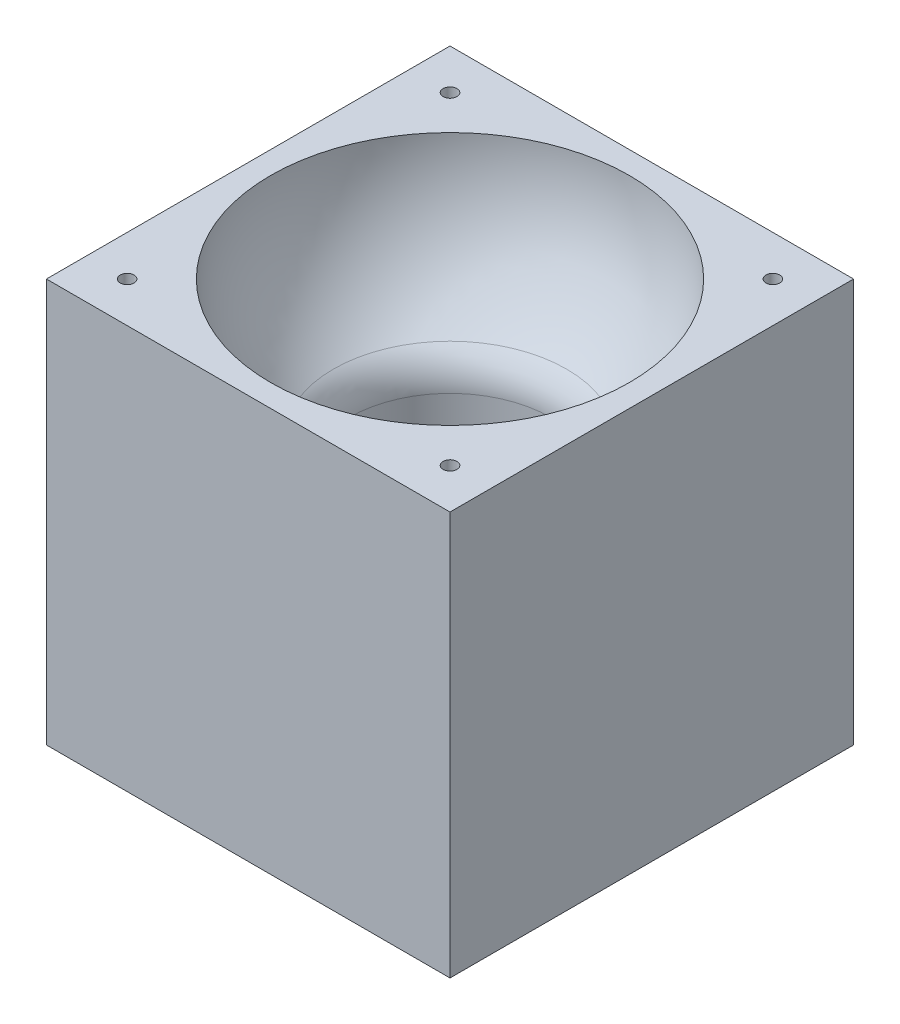
SolidWorks part; units mm, degrees
ref_plane "Front Plane" through (0, 0, 0) normal (0, 0, 1) x (1, 0, 0)
ref_plane "Top Plane" through (0, 0, 0) normal (0, 1, 0) x (1, 0, 0)
ref_plane "Right Plane" through (0, 0, 0) normal (1, 0, 0) x (0, 0, -1)
sketch "Sketch1" plane through (0, 0, 0) normal (0, 1, 0) x (1, 0, 0)
  line L1 (0, 0) -> (114.3, 0)
  line L2 (0, 0) -> (0, 114.3)
  line L3 (0, 114.3) -> (114.3, 114.3)
  line L4 (114.3, 0) -> (114.3, 114.3)
  dimension "D1" = 114.3
extrude "Boss-Extrude1" add sketch "Sketch1" along normal blind 114.3
sketch "Sketch2" plane through (0, 114.3, 0) normal (0, 1, 0) x (1, 0, 0)
  line L0 (57.15, 0) -> (57.15, 114.3) construction
  line L1 (0, 0) -> (114.3, 0) construction
  line L2 (114.3, 114.3) -> (0, 114.3) construction
  line L3 (57.15, 107.95) -> (57.15, 6.35)
  arc A0 (57.15, 107.95) -> (57.15, 6.35) centre (57.15, 57.15) ccw
  dimension "D1" = 101.6
revolve "Cut-Revolve1" cut sketch "Sketch2" angle 360 about L0
sketch "Sketch3" plane through (0, 114.3, 0) normal (0, 1, 0) x (1, 0, 0)
  line L0 (57.15, 114.3) -> (57.15, 0) construction
  line L1 (114.3, 114.3) -> (0, 114.3) construction
  line L2 (0, 0) -> (114.3, 0) construction
  circle A0 centre (57.15, 57.15) radius 28.575
  dimension "D1" = 57.15
extrude "Cut-Extrude1" cut sketch "Sketch3" against normal blind 107.95
sketch "Sketch4" plane through (0, 6.35, 0) normal (0, 1, 0) x (1, 0, 0)
  line L0 (57.15, 0) -> (57.15, 114.3) construction
  line L1 (0, 0) -> (114.3, 0) construction
  line L2 (114.3, 114.3) -> (0, 114.3) construction
  circle A0 centre (57.15, 57.15) radius 19.3675
  dimension "D1" = 38.735
extrude "Cut-Extrude2" cut sketch "Sketch4" against normal through all
shell "Shell1" thickness 6.35 removed face at (57.15, 0, -37.7825)
sketch "Sketch5" plane through (0, 0, 0) normal (0, -1, 0) x (1, 0, 0)
  circle A0 centre (57.15, -57.15) radius 25.7175
  circle A1 centre (57.15, -57.15) radius 19.3675 construction
  circle A2 centre (57.15, -57.15) radius 19.3675
  dimension "D1" = 6.35
extrude "Boss-Extrude2" [suppressed] add sketch "Sketch5" along normal blind 6.35
fillet "Fillet1" [suppressed] radius 6.35
fillet "Fillet2" radius 3.81 2 edges at (57.15, 69.0632, -22.225) (57.15, 0, -22.225)
sketch "Sketch6" plane through (0, 0, 0) normal (0, -1, 0) x (1, 0, 0)
  line L1 (107.95, -107.95) -> (6.35, -107.95)
  line L2 (107.95, -107.95) -> (107.95, -6.35)
  line L3 (107.95, -6.35) -> (6.35, -6.35)
  line L4 (0, 0) -> (0, -114.3)
  line L5 (0, -114.3) -> (114.3, -114.3)
  line L6 (114.3, -114.3) -> (114.3, 0)
  line L7 (114.3, 0) -> (0, 0)
  line L8 (0, 0) -> (0, -114.3)
  line L9 (0, -114.3) -> (114.3, -114.3)
  line L10 (114.3, -114.3) -> (114.3, 0)
  line L11 (114.3, 0) -> (0, 0)
  line L12 (6.35, -107.95) -> (6.35, -6.35)
  dimension "D1" = 0
extrude "Boss-Extrude3" [suppressed] add sketch "Sketch6" along normal blind 50.8
ref_plane "Plane1" through (57.15, 0, 0) normal (-1, 0, 0) x (0, 0, 1)
ref_plane "Plane2" through (0, 0, -57.15) normal (0, 0, 1) x (1, 0, 0)
sketch "Sketch8" plane through (0, 0, -57.15) normal (0, 0, 1) x (1, 0, 0)
  line L0 (57.15, 62.865) -> (57.15, -62.865) construction
  circle A0 centre (57.15, 33.9743) radius 9.525
  dimension "D1" = 19.05
extrude "Cut-Extrude4" cut sketch "Sketch8" against normal up to surface and the other way up to surface up to face at (57.15, 67.2286, -22.225) other way up to face at (57.15, 67.2286, -22.225)
sketch "Sketch9" plane through (0, 114.3, 0) normal (0, 1, 0) x (1, 0, 0)
  line L1 (11.43, 102.87) -> (102.87, 102.87) construction
  line L2 (11.43, 102.87) -> (11.43, 11.43) construction
  line L3 (11.43, 11.43) -> (102.87, 11.43) construction
  line L4 (102.87, 102.87) -> (102.87, 11.43) construction
  line L5 (11.43, 102.87) -> (102.87, 11.43) construction
  line L6 (11.43, 11.43) -> (102.87, 102.87) construction
  circle A0 centre (11.43, 102.87) radius 1.9685
  circle A1 centre (102.87, 102.87) radius 1.9685
  circle A2 centre (102.87, 11.43) radius 1.9685
  circle A3 centre (11.43, 11.43) radius 1.9685
  point P0 (57.15, 57.15)
  dimension "D2" = 3.937
  dimension "D1" = 91.44
extrude "Cut-Extrude5" cut sketch "Sketch9" against normal through all
pattern_circular "CirPattern1" count 4 every 45 about axis through (57.15, 6.35, -57.15) along (0, 1, 0) of "Cut-Extrude4"
sketch "Sketch12" plane through (0, 107.95, 0) normal (0, -1, 0) x (1, 0, 0)
  line L1 (106.6358, -104.0933) -> (105.8123, -100.2204)
  line L2 (105.8123, -100.2204) -> (102.0465, -98.9971)
  line L3 (102.0465, -98.9971) -> (99.1042, -101.6467)
  line L4 (99.1042, -101.6467) -> (99.9277, -105.5196)
  line L5 (99.9277, -105.5196) -> (103.6935, -106.7429)
  line L6 (103.6935, -106.7429) -> (106.6358, -104.0933)
  line L7 (14.3334, -105.5622) -> (15.2132, -101.7017)
  line L8 (15.2132, -101.7017) -> (12.3098, -99.0095)
  line L9 (12.3098, -99.0095) -> (8.5266, -100.1778)
  line L10 (8.5266, -100.1778) -> (7.6468, -104.0383)
  line L11 (7.6468, -104.0383) -> (10.5502, -106.7305)
  line L12 (10.5502, -106.7305) -> (14.3334, -105.5622)
  line L13 (14.3334, -8.7378) -> (10.5502, -7.5695)
  line L14 (10.5502, -7.5695) -> (7.6468, -10.2617)
  line L15 (7.6468, -10.2617) -> (8.5266, -14.1222)
  line L16 (8.5266, -14.1222) -> (12.3098, -15.2905)
  line L17 (12.3098, -15.2905) -> (15.2132, -12.5983)
  line L18 (15.2132, -12.5983) -> (14.3334, -8.7378)
  line L19 (106.6358, -10.2067) -> (103.6935, -7.5571)
  line L20 (103.6935, -7.5571) -> (99.9277, -8.7804)
  line L21 (99.9277, -8.7804) -> (99.1042, -12.6533)
  line L22 (99.1042, -12.6533) -> (102.0465, -15.3029)
  line L23 (102.0465, -15.3029) -> (105.8123, -14.0796)
  line L24 (105.8123, -14.0796) -> (106.6358, -10.2067)
  circle A0 centre (102.87, -102.87) radius 3.429 construction
  circle A1 centre (11.43, -102.87) radius 3.429 construction
  circle A2 centre (11.43, -11.43) radius 3.429 construction
  circle A3 centre (102.87, -11.43) radius 3.429 construction
  dimension "D1" = 6.858
extrude "Cut-Extrude7" cut sketch "Sketch12" against normal blind 3.175
fillet "Fillet3" radius 12.7 1 edges at (57.15, 72.2987, -28.575)
